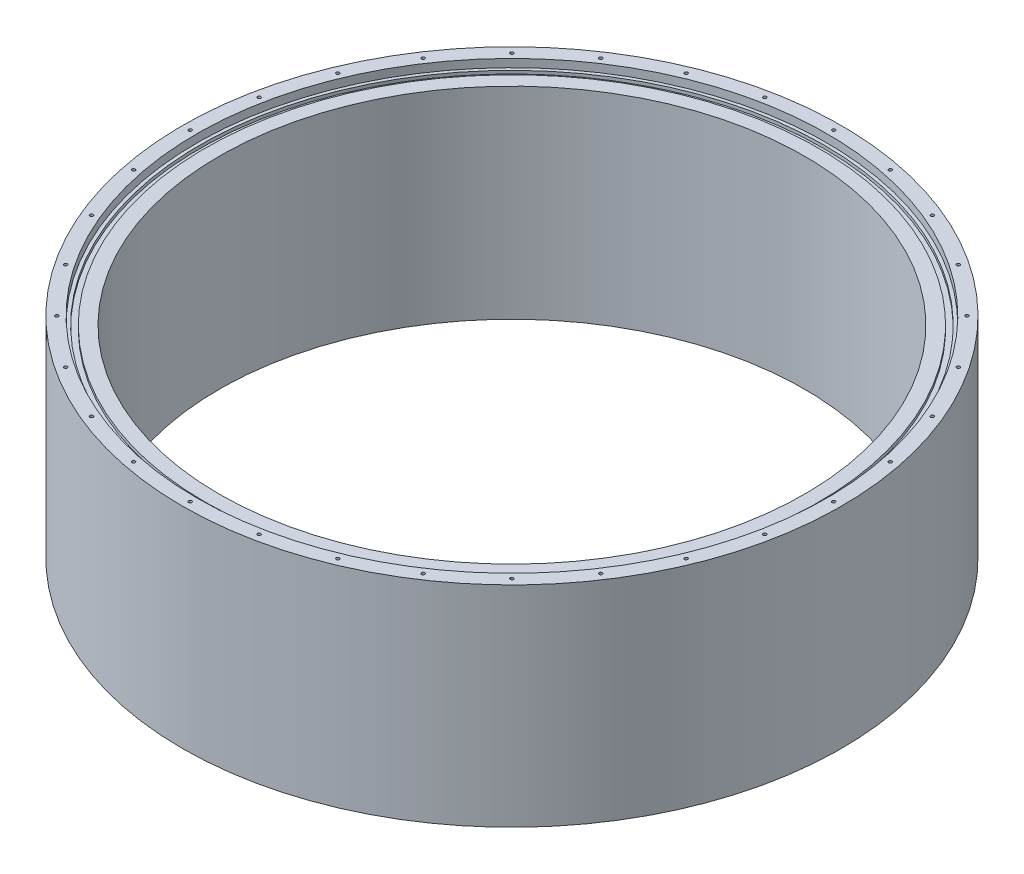
SolidWorks part; units mm, degrees
material "PVC Rigid"
ref_plane "Front" through (0, 0, 0) normal (0, 0, 1) x (1, 0, 0)
ref_plane "Top" through (0, 0, 0) normal (0, 1, 0) x (1, 0, 0)
ref_plane "Right" through (0, 0, 0) normal (1, 0, 0) x (0, 0, -1)
sketch "Sketch1" plane through (0, 0, 0) normal (0, 0, 1) x (1, 0, 0)
  line L0 (225.6, 74.685) -> (243, 74.685)
  line L1 (243, 74.685) -> (243, 80.885)
  line L2 (243, 80.885) -> (254, 80.885)
  line L3 (254, 80.885) -> (254, -80.885)
  line L4 (254, -80.885) -> (225.6, -80.885)
  line L5 (225.6, -80.885) -> (225.6, 74.685)
  line L6 (0, 80.885) -> (0, -80.885) construction
  line L7 (0, 0) -> (225.6, 0) construction
  dimension "D1" = 508
  dimension "D2" = 11
  dimension "D3" = 28.4
  dimension "D4" = 6.2
  dimension "D5" = 161.77
  dimension "D6" = 225.6
  dimension "D7" = 155.57
revolve "Revolve1" add sketch "Sketch1" angle 360 about L6
sketch "Sketch2" plane through (0, 0, 0) normal (0, 0, 1) x (1, 0, 0)
  line L0 (0, 80.885) -> (0, -80.885) construction
  line L1 (254, 80.885) -> (-254, 80.885) construction
  line L2 (-254, -80.885) -> (254, -80.885) construction
  line L3 (240.5, 72.272) -> (240.5, -77.587) construction
  line L4 (236.3344, 74.685) -> (240.5, 74.685)
  line L5 (236.3344, 74.685) -> (236.3344, 72.272)
  line L6 (236.3344, 72.272) -> (240.5, 72.272)
  line L7 (240.5, 74.685) -> (240.5, 72.272)
  line L8 (225.6, 74.685) -> (-225.6, 74.685) construction
  line L9 (225.6, 74.685) -> (-225.6, 74.685) construction
  line L10 (254, -80.885) -> (254, 80.885) construction
  line L12 (236.3344, -78.472) -> (240.5, -78.472) construction
  line L13 (236.3344, -78.472) -> (236.3344, -80.885) construction
  line L14 (236.3344, -80.885) -> (240.5, -80.885) construction
  line L15 (240.5, -78.472) -> (240.5, -80.885) construction
  dimension "D1" = 13.5
  dimension "D2" = 2.413
  dimension "D3" = 4.1656
revolve "Cut-Revolve1" cut sketch "Sketch2" angle 360 about L0
hole_wizard "M3x0.5 Tapped Hole1" positions "Sketch3" profile "Sketch4" tap size "M3x0.5" standard "ANSI Metric"
sketch "Sketch3" plane through (0, 80.885, 0) normal (0, 1, 0) x (1, 0, 0)
  point P0 (248, 0)
  dimension "D1" = 248
sketch "Sketch4" plane through (248, 80.885, 0) normal (1, 0, 0) x (0, 0, 1)
  line L0 (0, 0) -> (0, 10.2511)
  line L1 (0, 10.2511) -> (1.25, 9.5)
  line L2 (1.25, 9.5) -> (1.25, 0)
  line L5 (1.25, 0) -> (0, 0)
  line L10 (0, 10.2511) -> (-1.25, 9.5) construction
  line L11 (0, -6.35) -> (0, 107.95) construction
  dimension "Tap Drill Dia." = 2.5
  dimension "Tap Drill Depth" = 9.5
  dimension "Drill Angle" = 118
cosmetic thread "Hole Thread1" parameters "D1"=8, "D2"=3
pattern_circular "CirPattern1" count 32 over 360 about axis through (0, 80.885, 0) along (0, 1, 0) of "M3x0.5 Tapped Hole1"
mirror "Mirror1" about plane through (0, 0, 0) normal (0, 1, 0) of "CirPattern1"
hole_wizard "Ø5.0mm Dowel Hole1" positions "Sketch5" profile "Sketch6" hole size "Ø5.0" standard "ANSI Metric"
sketch "Sketch5" plane through (0, -80.885, 0) normal (0, -1, 0) x (-1, 0, 0)
  line L2 (0, 0) -> (0, 204.5498) construction
  line L3 (-24.2102, 245.8106) -> (0, 0) construction
  line L4 (0, 0) -> (24.9245, -253.0623) construction
  circle A1 centre (0, 0) radius 247
  point P6 (-24.2102, 245.8106)
  point P8 (24.2102, -245.8106)
  dimension "D2" = 494
  dimension "D1" = 5.625
sketch "Sketch6" plane through (-24.2102, -80.885, 245.8106) normal (1, 0, 0) x (0, 0, -1)
  line L0 (0, 0) -> (0, 7.5172)
  line L1 (0, 7.5172) -> (2.525, 6)
  line L2 (2.525, 6) -> (2.525, 0)
  line L5 (2.525, 0) -> (0, 0)
  line L10 (0, 7.5172) -> (-2.525, 6) construction
  line L11 (0, -6.35) -> (0, 107.95) construction
  dimension "Hole Dia." = 5.05
  dimension "Hole Depth" = 6
  dimension "Drill Angle" = 118
